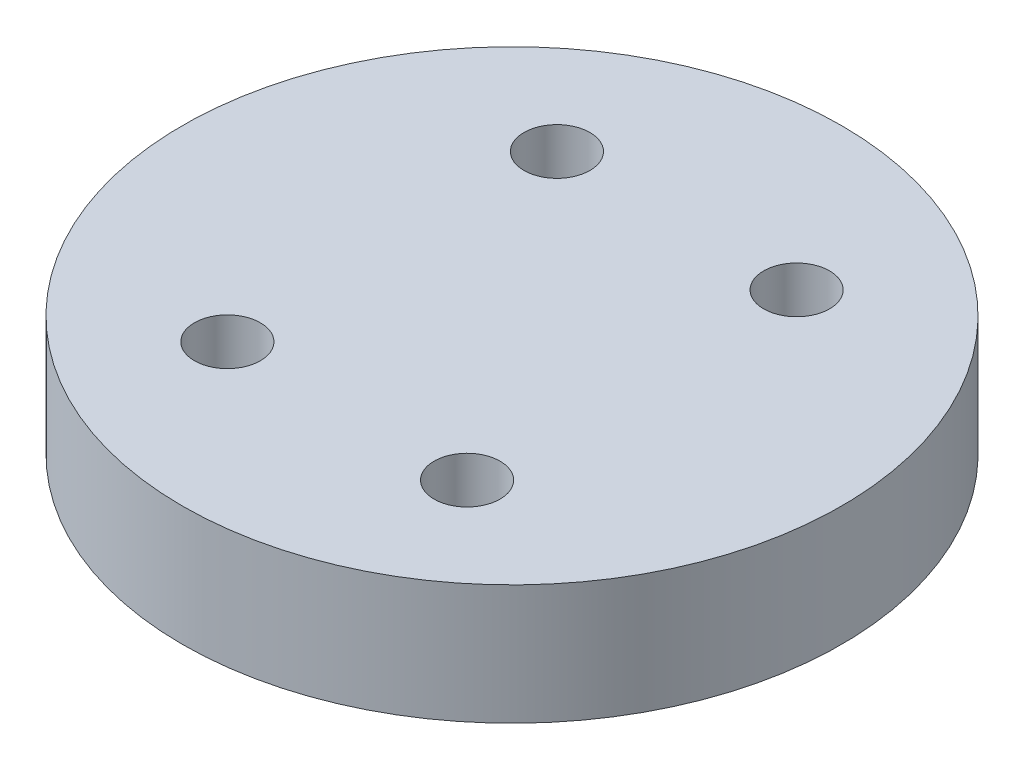
SolidWorks part; units mm, degrees
ref_plane "Front Plane" through (0, 0, 0) normal (0, 0, 1) x (1, 0, 0)
ref_plane "Top Plane" through (0, 0, 0) normal (0, 1, 0) x (1, 0, 0)
ref_plane "Right Plane" through (0, 0, 0) normal (1, 0, 0) x (0, 0, -1)
sketch "Sketch1" plane through (0, 0, 0) normal (0, 1, 0) x (1, 0, 0)
  line L0 (0, 0) -> (0, 68.5524) construction
  line L1 (0, 52.4907) -> (0, -49.3242) construction
  line L2 (10, -13.75) -> (10, 13.75)
  line L3 (10, -13.75) -> (-10, -13.75)
  line L4 (10, 13.75) -> (-10, 13.75)
  line L5 (-10, -13.75) -> (-10, 13.75)
  line L6 (10, -13.75) -> (-10, 13.75) construction
  line L7 (10, 13.75) -> (-10, -13.75) construction
  circle A0 centre (0, 0) radius 27.5
  circle A1 centre (-10, 13.75) radius 2.75
  circle A2 centre (10, 13.75) radius 2.75
  circle A3 centre (10, -13.75) radius 2.75
  circle A4 centre (-10, -13.75) radius 2.75
  dimension "D1" = 55
  dimension "D5" = 5.5
  dimension "D3" = 27.5
  dimension "D4" = 20
extrude "Boss-Extrude1" add sketch "Sketch1" along normal blind 10 contours A0 A4 L5 A1 L4 A2 L2 A3 L3 | A4 L3 A3 L2 A2 L4 A1 L5 region at (0, 0, 0) region at (-26.7222, 0, 0)
equation "\"LOGO_SIZE\"= 40"
equation "\"SECTION_SIZE\"= \"LOGO_SIZE\" / 6"
